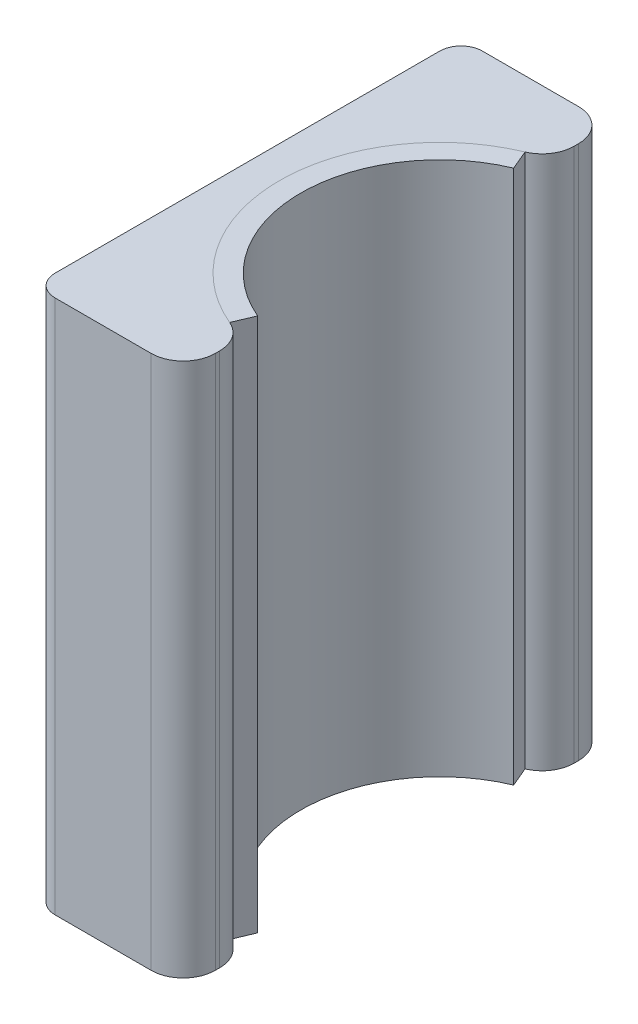
SolidWorks part; units mm, degrees
material "ABS"
ref_plane "正面" through (0, 0, 0) normal (0, 0, 1) x (1, 0, 0)
ref_plane "平面" through (0, 0, 0) normal (0, 1, 0) x (1, 0, 0)
ref_plane "右側面" through (0, 0, 0) normal (1, 0, 0) x (0, 0, -1)
sketch "ｽｹｯﾁ1" plane through (0, 0, 0) normal (0, 1, 0) x (1, 0, 0)
  line L0 (0, 20) -> (0, -20)
  line L1 (0, 0) -> (95.312, 0) construction
  line L2 (0, 20) -> (11, 20)
  line L3 (14, 17) -> (14, 16.5831)
  line L4 (14, -16.5831) -> (14, -17)
  line L5 (11, -20) -> (0, -20)
  arc A0 (12.1667, 13.8193) -> (12.1667, -13.8193) centre (18, 0) ccw
  arc A1 (14, -17) -> (11, -20) centre (11, -17) cw
  arc A2 (11, 20) -> (14, 17) centre (11, 17) cw
  arc A3 (14, -16.5831) -> (12.1667, -13.8193) centre (11, -16.5831) ccw
  arc A4 (14, 16.5831) -> (12.1667, 13.8193) centre (11, 16.5831) cw
  point P8 (19.1906, 0)
  point P11 (0, 0)
  point P12 (0, 0)
  point P13 (12.5, 0)
  point P14 (17.9787, 0)
  point P19 (14, 20)
  point P24 (14, 14.4568)
  dimension "D1" = 15
  dimension "D5" = 3
  dimension "D2" = 40
  dimension "D3" = 14
  dimension "D4" = 4
extrude "ﾎﾞｽ - 押し出し1" add sketch "ｽｹｯﾁ1" along normal blind 25 and the other way blind 25
sketch "ｽｹｯﾁ2" plane through (14, 0, 0) normal (1, 0, 0) x (0, 0, -1)
  line L0 (-17, 25) -> (17, 25) construction
  line L1 (0, 25) -> (0, -14.7101) construction
  line L2 (55, 0) -> (-55, 0) construction
  circle A0 centre (0, 10.5) radius 1.1
  circle A1 centre (0, -10.5) radius 1.1
  dimension "D1" = 2.2
  dimension "D2" = 10.5
extrude "ｶｯﾄ - 押し出し1" cut sketch "ｽｹｯﾁ2" against normal through all
ref_plane "平面1" through (10, 0, 0) normal (-1, 0, 0) x (0, 0, 1)
sketch "ｽｹｯﾁ3" plane through (10, 0, 0) normal (-1, 0, 0) x (0, 0, 1)
  circle A0 centre (0, 10.5) radius 3
  circle A1 centre (0, -10.5) radius 3
  circle A2 centre (0, -10.5) radius 1.1 construction
  circle A3 centre (0, 10.5) radius 1.1 construction
  dimension "D1" = 6
extrude "ｶｯﾄ - 押し出し2" cut sketch "ｽｹｯﾁ3" along normal blind 8
fillet "ﾌｨﾚｯﾄ1" radius 2 2 edges at (0, 0, 20) (0, 0, -20)
sketch "ｽｹｯﾁ5" plane through (0, 25, 0) normal (0, 1, 0) x (1, 0, 0)
  line L0 (12.1667, 13.8193) -> (12.9444, 11.9767)
  line L1 (12.9444, -11.9767) -> (12.1667, -13.8193)
  arc A0 (12.1667, 13.8193) -> (12.1667, -13.8193) centre (18, 0) ccw construction
  arc A1 (12.1667, 13.8193) -> (12.1667, -13.8193) centre (18, 0) ccw
  arc A2 (12.9444, 11.9767) -> (12.9444, -11.9767) centre (18, 0) ccw
  point P9 (13.5558, 11.1527)
  point P14 (13.4839, 12.1469)
  point P15 (13.4839, 12.1469)
  dimension "D1" = 26
extrude "ﾎﾞｽ - 押し出し2" add sketch "ｽｹｯﾁ5" against normal up to surface (50 mm away) separate body up to face at (8.2012, -25, 0)
